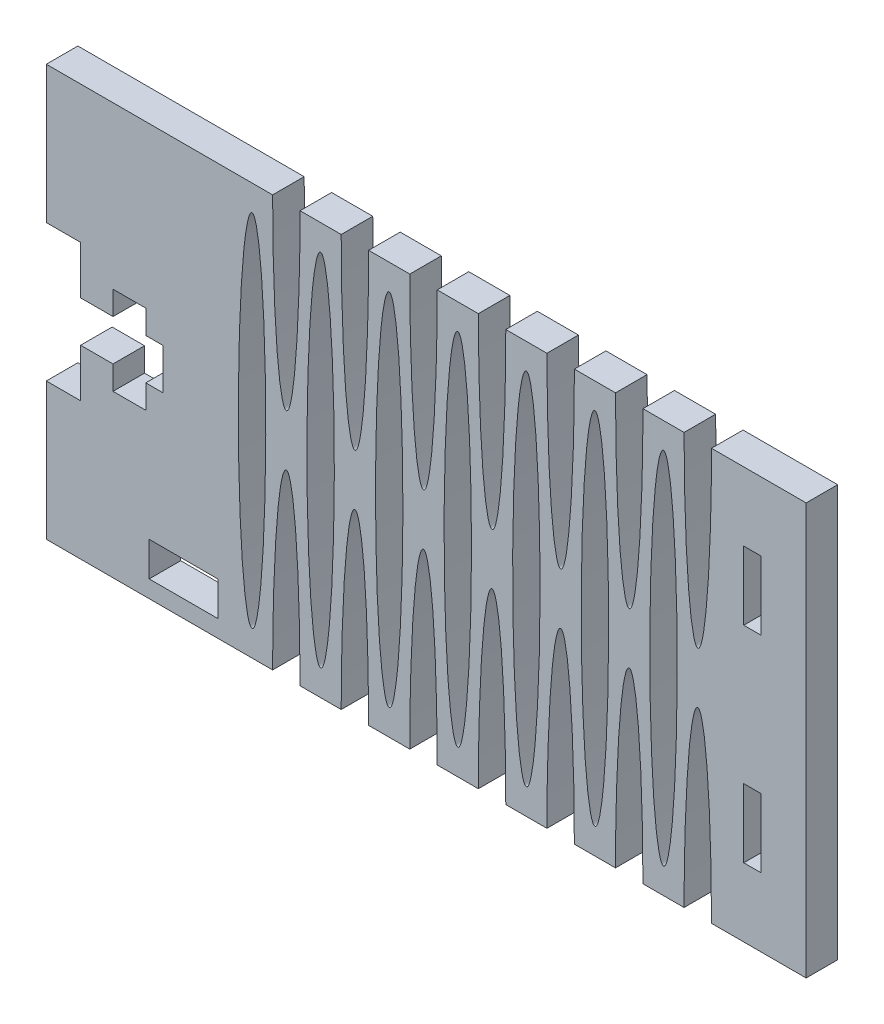
SolidWorks part; units mm, degrees
ref_plane "Front Plane" through (0, 0, 0) normal (0, 0, 1) x (1, 0, 0)
ref_plane "Top Plane" through (0, 0, 0) normal (0, 1, 0) x (1, 0, 0)
ref_plane "Right Plane" through (0, 0, 0) normal (1, 0, 0) x (0, 0, -1)
sketch "Sketch1" plane through (0, 0, -35.179) normal (0, 0, -1) x (-1, 0, 0)
  line L0 (-2.921, 36.5125) -> (0, 36.5125) construction
  line L1 (0, -1.5875) -> (-70.358, -1.5875)
  line L2 (0, -1.5875) -> (0, 36.5125)
  line L3 (0, 36.5125) -> (-70.358, 36.5125)
  line L4 (-70.358, -1.5875) -> (-70.358, 36.5125)
  dimension "D1" = 70.358
extrude "Boss-Extrude1" add sketch "Sketch1" along normal blind 2.921 contours L1 L4 L3 L2
sketch "Sketch2" plane through (0, 0, -38.1) normal (0, 0, -1) x (-1, 0, 0)
  line L0 (-3.175, 23.8125) -> (-3.175, 11.1125) construction
  line L1 (-3.175, 11.1125) -> (0, 11.1125) construction
  line L2 (0, 11.1125) -> (0, 23.8125) construction
  line L3 (0, 23.8125) -> (-3.175, 23.8125) construction
  line L4 (-15.875, 3.175) -> (-15.875, 0) construction
  line L5 (-15.875, 0) -> (-9.525, 0) construction
  line L6 (-9.525, 0) -> (-9.525, 3.175) construction
  line L7 (-9.525, 3.175) -> (-15.875, 3.175) construction
  line L8 (-3.175, 23.8125) -> (-3.175, 11.1125)
  line L9 (-3.175, 11.1125) -> (0, 11.1125)
  line L10 (0, 11.1125) -> (0, 23.8125)
  line L11 (0, 23.8125) -> (-3.175, 23.8125)
  line L12 (-15.875, 3.175) -> (-15.875, 0)
  line L13 (-15.875, 0) -> (-9.525, 0)
  line L14 (-9.525, 0) -> (-9.525, 3.175)
  line L15 (-9.525, 3.175) -> (-15.875, 3.175)
extrude "Cut-Extrude1" cut sketch "Sketch2" against normal through all
sketch "Sketch3" plane through (0, 0, -38.1) normal (0, 0, -1) x (-1, 0, 0)
  line L0 (-9.2075, 19.3612) -> (-10.795, 19.3612) construction
  line L1 (-10.795, 19.3612) -> (-10.795, 15.5639) construction
  line L2 (-10.795, 15.5639) -> (-9.2075, 15.5639) construction
  line L3 (-9.2075, 15.5639) -> (-9.2075, 13.3667) construction
  line L4 (-9.2075, 13.3667) -> (-6.1754, 13.3667) construction
  line L5 (-6.1754, 13.3667) -> (-6.1754, 15.5638) construction
  line L6 (-6.1754, 15.5638) -> (-3.175, 15.5638) construction
  line L7 (-9.2075, 21.5583) -> (-9.2075, 19.3612) construction
  line L8 (-6.1754, 21.5583) -> (-9.2075, 21.5583) construction
  line L9 (-6.1754, 19.3612) -> (-6.1754, 21.5583) construction
  line L10 (-3.175, 19.3612) -> (-6.1754, 19.3612) construction
  line L11 (-9.2075, 19.3612) -> (-10.795, 19.3612)
  line L12 (-10.795, 19.3612) -> (-10.795, 15.5639)
  line L13 (-10.795, 15.5639) -> (-9.2075, 15.5639)
  line L14 (-9.2075, 15.5639) -> (-9.2075, 13.3667)
  line L15 (-9.2075, 13.3667) -> (-6.1754, 13.3667)
  line L16 (-6.1754, 13.3667) -> (-6.1754, 15.5638)
  line L17 (-6.1754, 15.5638) -> (-3.175, 15.5638)
  line L18 (-9.2075, 21.5583) -> (-9.2075, 19.3612)
  line L19 (-6.1754, 21.5583) -> (-9.2075, 21.5583)
  line L20 (-6.1754, 19.3612) -> (-6.1754, 21.5583)
  line L21 (-3.175, 19.3612) -> (-6.1754, 19.3612)
extrude "Cut-Extrude2" cut sketch "Sketch3" against normal through all
sketch "Sketch4" plane through (0, 0, -35.179) normal (0, 0, 1) x (1, 0, 0)
  line L0 (19.05, -1.5875) -> (19.05, 36.5125) construction
  line L1 (0, -1.5875) -> (70.358, -1.5875) construction
  line L2 (0, 36.5125) -> (70.358, 36.5125) construction
  line L3 (0, 23.8125) -> (0, 36.5125) construction
  line L4 (64.008, 36.5125) -> (64.008, -1.5875) construction
  line L5 (70.358, -1.5875) -> (70.358, 36.5125) construction
  line L6 (70.358, 17.4625) -> (-6.8374, 17.4625) construction
  ellipse E0 centre (19.05, 17.4625) end of major axis (19.05, 0.7937) minor radius 1.27
  ellipse E1 centre (22.225, -1.5875) end of major axis (22.225, 15.0812) minor radius 1.27
  ellipse E2 centre (22.225, 36.5125) end of major axis (22.225, 19.8437) minor radius 1.27
  line M9 (0, -1.5875) -> (70.358, -1.5875)
  dimension "D1" = 19.05
  dimension "D2" = 6.35
  dimension "D3" = 33.3375
  dimension "D4" = 2.54
  dimension "D5" = 2.54
  dimension "D6" = 33.3375
  dimension "D7" = 3.175
  dimension "D8" = 33.3375
  dimension "D9" = 2.54
extrude "Cut-Extrude3" cut sketch "Sketch4" against normal through all contours E0 | E1 M9 | E1 M9 | E2 region at (19.05, 17.4625, -35.179) region at (22.225, 5.4869, -35.179) region at (22.225, -8.6619, -35.179)
pattern_linear "LPattern1" count 7 spacing 6.35 along (1, 0, 0) of "Cut-Extrude3"
sketch "Sketch5" plane through (0, 0, -35.179) normal (0, 0, 1) x (1, 0, 0)
  line L0 (61.595, -1.5875) -> (70.358, -1.5875) construction
  line L1 (64.5795, 23.8125) -> (66.167, 23.8125)
  line L2 (64.5795, 23.8125) -> (64.5795, 30.1625)
  line L3 (64.5795, 30.1625) -> (66.167, 30.1625)
  line L4 (66.167, 23.8125) -> (66.167, 30.1625)
  line L5 (64.5795, 11.1125) -> (66.167, 11.1125)
  line L6 (64.5795, 11.1125) -> (64.5795, 4.7625)
  line L7 (64.5795, 4.7625) -> (66.167, 4.7625)
  line L8 (66.167, 11.1125) -> (66.167, 4.7625)
  line L9 (61.595, 36.5125) -> (70.358, 36.5125) construction
  line L10 (70.358, -1.5875) -> (70.358, 36.5125) construction
  dimension "D1" = 6.35
  dimension "D2" = 6.35
  dimension "D3" = 1.5875
  dimension "D4" = 6.35
  dimension "D5" = 6.35
  dimension "D6" = 1.5875
  dimension "D7" = 4.191
extrude "Cut-Extrude4" cut sketch "Sketch5" against normal through all
equation "\"D1@Boss-Extrude1\"=\"thick@boxassy1.sldasm\""
equation "\"D7@Sketch5\"=\"thick@boxassy1.sldasm\"+0.05"
